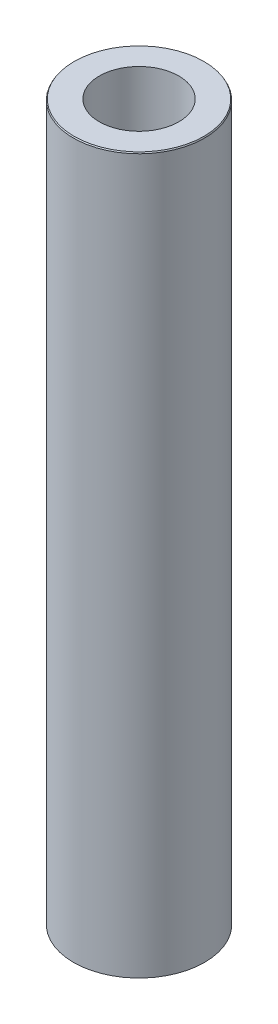
SolidWorks part; units mm, degrees
ref_plane "Front Plane" through (0, 0, 0) normal (0, 0, 1) x (1, 0, 0)
ref_plane "Top Plane" through (0, 0, 0) normal (0, 1, 0) x (1, 0, 0)
ref_plane "Right Plane" through (0, 0, 0) normal (1, 0, 0) x (0, 0, -1)
sketch "Sketch1" plane through (0, 0, 0) normal (0, 1, 0) x (1, 0, 0)
  circle A0 centre (0, 0) radius 17.5
  dimension "SHAFT_OD" = 35
extrude "Boss-Extrude1" add sketch "Sketch1" along normal blind 190.9976
sketch "Sketch2" plane through (0, 0, 0) normal (0, 1, 0) x (1, 0, 0)
  circle A0 centre (0, 0) radius 10.6065
  dimension "BORE_D" = 21.2129
extrude "Cut-Extrude1" cut sketch "Sketch2" along normal through all
chamfer "Chamfer1" distance 0.3168 angle 30 2 edges at (0, 190.9976, 17.5) (0, 0, 17.5) first distance on face at (0, 190.9976, 17.5) first distance on face at (0, 0, 10.6065)
